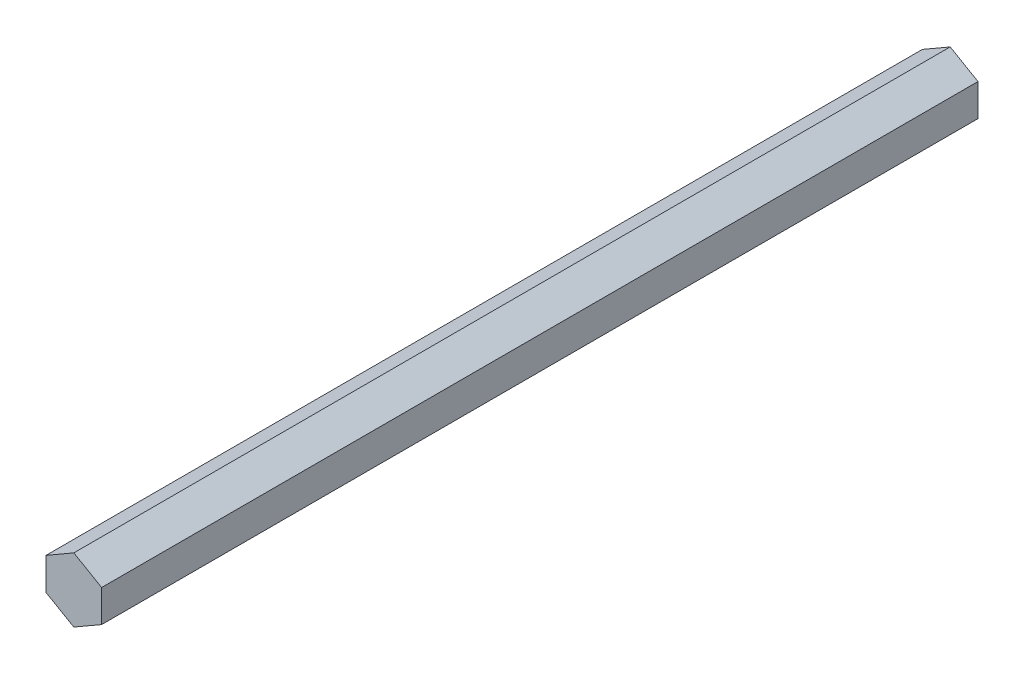
SolidWorks part; units mm, degrees
ref_plane "Front Plane" through (0, 0, 0) normal (0, 0, 1) x (1, 0, 0)
ref_plane "Top Plane" through (0, 0, 0) normal (0, 1, 0) x (1, 0, 0)
ref_plane "Right Plane" through (0, 0, 0) normal (1, 0, 0) x (0, 0, -1)
sketch "Sketch1" plane through (0, 0, 0) normal (0, 0, 1) x (1, 0, 0)
  line L1 (6.35, 3.6662) -> (0, 7.3323)
  line L2 (0, 7.3323) -> (-6.35, 3.6662)
  line L3 (-6.35, 3.6662) -> (-6.35, -3.6662)
  line L4 (-6.35, -3.6662) -> (0, -7.3323)
  line L5 (0, -7.3323) -> (6.35, -3.6662)
  line L6 (6.35, -3.6662) -> (6.35, 3.6662)
  circle A0 centre (0, 0) radius 6.35 construction
  point P11 (0, 0)
  dimension "D1" = 12.7
extrude "Boss-Extrude1" add sketch "Sketch1" along normal mid plane 200
ref_axis "Axis2" through (0, 0, 0) along (0, 0, 1)
